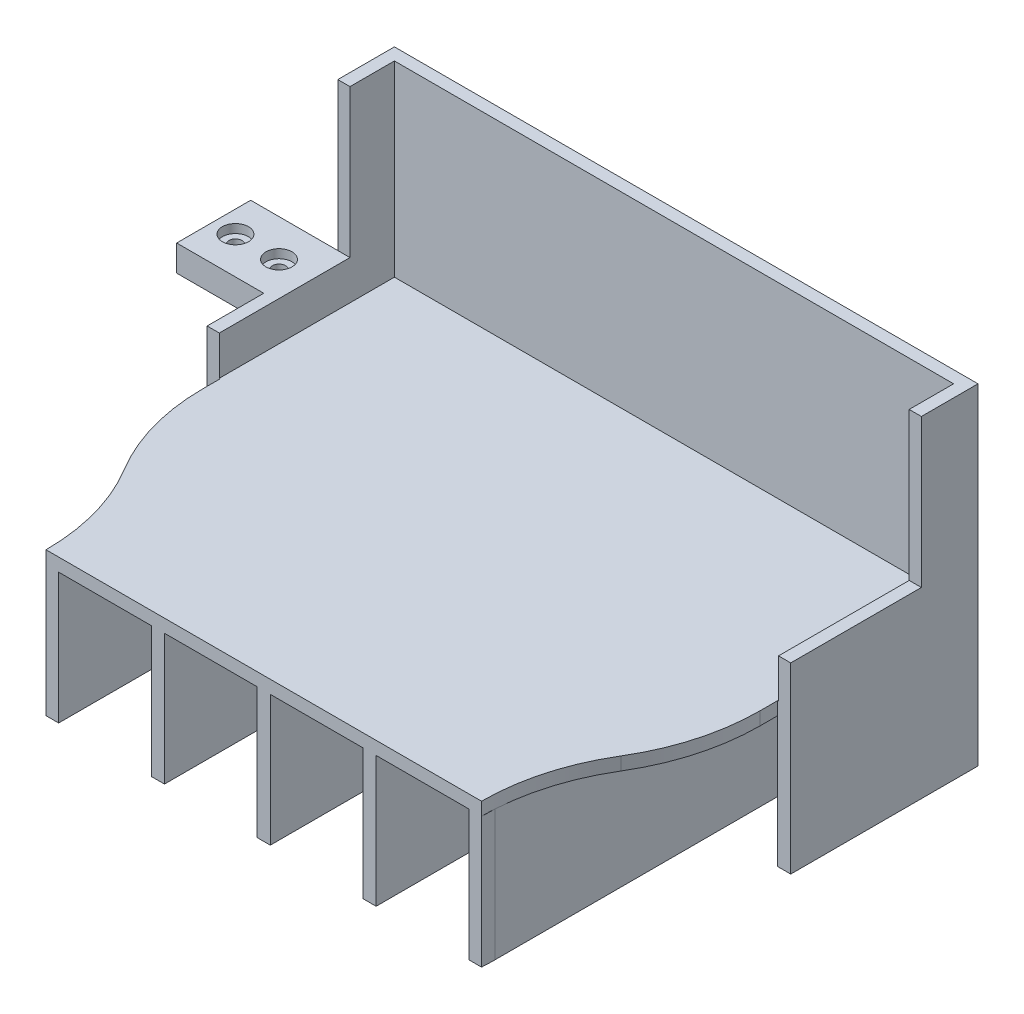
SolidWorks part; units mm, degrees
ref_plane "前视基准面" through (0, 0, 0) normal (0, 0, 1) x (1, 0, 0)
ref_plane "上视基准面" through (0, 0, 0) normal (0, 1, 0) x (1, 0, 0)
ref_plane "右视基准面" through (0, 0, 0) normal (1, 0, 0) x (0, 0, -1)
other "Configuration Table"
sketch "草图1" plane through (0, 0, 0) normal (0, 1, 0) x (1, 0, 0)
  line L6 (0, -20) -> (50, -20)
  line L23 (0, -20) -> (-50, -20)
  line L25 (-1, 70) -> (-1, 30)
  line L26 (1, 70) -> (41, 70)
  line L27 (43, 52) -> (85, 52)
  line L32 (1, 30) -> (41, 30)
  line L36 (1, 70) -> (1, 30)
  line L37 (-41, 30) -> (-1, 30)
  line L38 (-41, 70) -> (-1, 70)
  line L39 (-43, 72) -> (43, 72)
  line L40 (-43, 50) -> (-43, 10)
  line L41 (-41, 70) -> (-41, 30)
  line L42 (-43, 10) -> (-83, 10)
  line L43 (-83, 10) -> (-83, 50)
  line L44 (-83, 50) -> (-43, 50)
  line L45 (41, 70) -> (41, 30)
  line L46 (85, 8) -> (85, 52)
  line L48 (43, 10) -> (83, 10)
  line L49 (43, 52) -> (43, 72)
  line L50 (43, 50) -> (43, 10)
  line L51 (83, 10) -> (83, 50)
  line L52 (43, 50) -> (83, 50)
  line L61 (50, -20) -> (57, -20)
  line L63 (-50, -20) -> (-57, -20)
  line L64 (-85, 50) -> (-85, 8)
  line L65 (-85, 50) -> (-85, 52)
  line L66 (-85, 52) -> (-43, 52)
  line L67 (-43, 52) -> (-43, 72)
  circle A0 centre (18, 0) radius 10
  circle A1 centre (-18, 0) radius 10
  arc A3 (85, 8) -> (57, -20) centre (57, 8) cw
  arc A4 (-57, -20) -> (-85, 8) centre (-57, 8) cw
extrude "凸台-拉伸1" add sketch "草图1" along normal blind 2
sketch "草图2" plane through (0, 0, 0) normal (0, -1, 0) x (1, 0, 0)
  line L0 (-85, -8) -> (-85, -52)
  line L1 (-85, -52) -> (-43, -52)
  line L2 (-43, -52) -> (-43, -72)
  line L3 (-43, -72) -> (43, -72)
  line L4 (43, -72) -> (43, -52)
  line L5 (43, -52) -> (85, -52)
  line L6 (85, -52) -> (85, -8)
  line L7 (-57, 20) -> (57, 20)
  arc A0 (-85, -8) -> (-57, 20) centre (-57, -8) cw
  arc A1 (57, 20) -> (85, -8) centre (57, -8) cw
  circle A2 centre (-18, 0) radius 10
  circle A3 centre (18, 0) radius 10
extrude "凸台-拉伸2" add sketch "草图2" along normal blind 2
sketch "草图4" plane through (0, 2, 0) normal (0, 1, 0) x (1, 0, 0)
  line L0 (0, -20) -> (-50, -20)
  line L1 (-57, -20) -> (57, -20) construction
  line L2 (-50, -20) -> (50, -20)
  arc A0 (-50, -20) -> (50, -20) centre (0, -20) cw
  circle A3 centre (-18, 0) radius 15
  circle A4 centre (18, 0) radius 15
  line M14 (-57, -20) -> (57, -20)
extrude "凸台-拉伸3" add sketch "草图4" along normal blind 8 contours A0 A4 A3 M14 region at (0, 2, -1.9073)
loft "切除-放样1" cut section edge at (-18, 10, 15) section edge at (-18, 2, 10) end constraint default connector at (-3.9419, 10, -5.2315) connector at (-9.8366, 2, -5.7757)
sketch "草图5" plane through (0, 2, 0) normal (0, 1, 0) x (1, 0, 0)
  circle A0 centre (-18, 0) radius 10
sketch "草图6" plane through (0, 10, 0) normal (0, 1, 0) x (1, 0, 0)
  circle A0 centre (-18, 0) radius 15
sketch "草图7" plane through (0, 10, 0) normal (0, 1, 0) x (1, 0, 0)
  circle A0 centre (-18, 0) radius 15
  circle A1 centre (-18, 0) radius 10
extrude "凸台-拉伸4" add sketch "草图7" against normal blind 8 contours A0 | A1
loft "切除-放样2" cut profiles "草图6", "草图5" connector at (-3.6249, 10, -4.2843) connector at (-10.0221, 2, -6.0293)
sketch "草图9" plane through (0, 2, 0) normal (0, 1, 0) x (1, 0, 0)
  circle A0 centre (18, 0) radius 10
sketch "草图10" plane through (0, 10, 0) normal (0, 1, 0) x (1, 0, 0)
  circle A0 centre (18, 0) radius 15
sketch "草图11" plane through (0, 10, 0) normal (0, 1, 0) x (1, 0, 0)
  circle A0 centre (18, 0) radius 10
  circle A1 centre (18, 0) radius 15
extrude "凸台-拉伸5" add sketch "草图11" against normal blind 8
loft "切除-放样3" cut profiles "草图10", "草图9" connector at (32.657, 10, -3.1893) connector at (26.6644, 2, -4.9927)
fillet "圆角1" radius 8 1 edges at (0, 10, -30)
sketch "草图20" plane through (0, 2, 0) normal (0, 1, 0) x (1, 0, 0)
  circle A0 centre (-18, 0) radius 10
  circle A1 centre (18, 0) radius 10
extrude "凸台-拉伸7" add sketch "草图20" against normal blind 1
sketch "草图21" plane through (0, 2, 0) normal (0, 1, 0) x (1, 0, 0)
  line L0 (-42, -20) -> (42, -20) construction
  line L1 (-50, -20) -> (-42, -20) construction
  line L2 (-50, -20) -> (-103.4635, -20)
  line L3 (-103.4635, -20) -> (-103.4635, 85.0865)
  line L4 (50, -20) -> (103.2152, -20)
  line L5 (103.2152, -20) -> (103.2152, 85.0865)
  line L6 (103.2152, 85.0865) -> (-103.4635, 85.0865)
  arc A0 (-50, -20) -> (50, -20) centre (0, -20) cw
  arc A1 (50, -20) -> (-50, -20) centre (0, -20) ccw construction
extrude "切除-拉伸2" cut sketch "草图21" against normal blind 4
sketch "草图22" plane through (0, -2, 0) normal (0, -1, 0) x (1, 0, 0)
  line L22 (-64, -30) -> (-64, -74)
  line L23 (-64, -74) -> (0, -74)
  line L24 (64, -30) -> (64, -74)
  line L25 (64, -74) -> (0, -74)
  line L28 (50, 20) -> (-50, 20) construction
  arc A1 (-50, 20) -> (-57, -5) centre (-98.1429, 20) cw
  arc A2 (-64, -30) -> (-57, -5) centre (-15.8571, -30) cw
  arc A3 (64, -30) -> (57, -5) centre (15.8571, -30) ccw
  arc A4 (57, -5) -> (50, 20) centre (98.1429, 20) cw
  arc A5 (-50, 20) -> (50, 20) centre (0, 20) ccw
extrude "凸台-拉伸8" add sketch "草图22" against normal blind 4
sketch "草图28" plane through (0, -2, 0) normal (0, -1, 0) x (1, 0, 0)
  circle A0 centre (-18, 0) radius 10
  circle A1 centre (18, 0) radius 10
extrude "凸台-拉伸10" add sketch "草图28" against normal blind 4
sketch "草图29" plane through (0, 2, 0) normal (0, 1, 0) x (1, 0, 0)
  circle A0 centre (-18, 0) radius 10
  circle A1 centre (18, 0) radius 10
extrude "切除-拉伸5" cut sketch "草图29" against normal blind 3
sketch "草图31" plane through (0, 10, 0) normal (0, 1, 0) x (1, 0, 0)
  line L0 (-50, -20) -> (50, -20)
  arc A0 (-50, -20) -> (50, -20) centre (0, -20) cw
extrude "切除-拉伸6" cut sketch "草图31" against normal blind 8
sketch "草图32" plane through (0, 2, 0) normal (0, 1, 0) x (1, 0, 0)
  circle A0 centre (-18, 0) radius 10
  circle A1 centre (18, 0) radius 10
extrude "凸台-拉伸11" add sketch "草图32" against normal blind 4
sketch "草图33" plane through (0, 0, -74) normal (0, 0, -1) x (-1, 0, 0)
  line L0 (64, 2) -> (64, -2) construction
  line L1 (-64, 2) -> (64, 2)
  line L2 (-64, 2) -> (-64, 1)
  line L3 (-64, 1) -> (64, 1)
  line L4 (64, 2) -> (64, 1)
extrude "切除-拉伸7" cut sketch "草图33" against normal blind 100
sketch "草图34" plane through (0, 1, 0) normal (0, 1, 0) x (1, 0, 0)
  line L1 (-64, 74) -> (64, 74)
  line L2 (-64, 74) -> (-64, 77)
  line L3 (-64, 77) -> (64, 77)
  line L4 (64, 74) -> (64, 77)
  line L5 (64, 77) -> (67, 77)
  line L6 (64, 77) -> (64, 34)
  line L7 (64, 34) -> (67, 34)
  line L8 (67, 77) -> (67, 34)
  line L9 (-64, 77) -> (-67, 77)
  line L10 (-64, 77) -> (-64, 34)
  line L11 (-64, 34) -> (-67, 34)
  line L12 (-67, 77) -> (-67, 34)
  line M16 (64, 30) -> (64, 74)
  line M17 (64, 74) -> (-64, 74)
  line M18 (-64, 74) -> (-64, 30)
extrude "凸台-拉伸12" add sketch "草图34" along normal blind 42 separate body contours L8 L5 L4 L7 M16 | L4 L3 L2 M17 | L9 L12 L11 L2 M18 region at (0, 1, -75.5) region at (-65.5, 1, -55.5) region at (65.5, 1, -55.5)
sketch "草图35" plane through (0, -2, 0) normal (0, -1, 0) x (1, 0, 0)
  line L0 (-67, -77) -> (67, -77) construction
  line L1 (-67, -34) -> (-64, -34)
  line L2 (-67, -34) -> (-67, -77)
  line L3 (-67, -77) -> (-64, -77)
  line L4 (-64, -34) -> (-64, -77)
  line L6 (-64, -77) -> (64, -77)
  line L7 (-64, -77) -> (-64, -74)
  line L8 (-64, -74) -> (64, -74)
  line L9 (64, -77) -> (64, -74)
  line L10 (67, -34) -> (64, -34)
  line L11 (67, -34) -> (67, -77)
  line L12 (67, -77) -> (64, -77)
  line L13 (64, -34) -> (64, -77)
  line M9 (-64, -74) -> (64, -74)
  line M10 (64, -74) -> (64, -30)
extrude "凸台-拉伸13" add sketch "草图35" against normal blind 3 contours L6 L9 L4 M9 | L12 L11 L10 L9 M10 | L3 L2 L1 L4 region at (0, -2, -75.5) region at (65.5, -2, -55.5)
sketch "草图36" plane through (0, -2, 0) normal (0, -1, 0) x (1, 0, 0)
  line L0 (-67, -77) -> (67, -77) construction
  line L1 (-67, -34) -> (-64, -34)
  line L2 (-67, -34) -> (-67, -77)
  line L3 (-67, -77) -> (-64, -77)
  line L4 (-64, -34) -> (-64, -77)
  line L5 (64, -34) -> (64, -74)
  line L6 (64, -34) -> (67, -34)
  line L8 (64, -77) -> (67, -77)
  line L9 (67, -34) -> (67, -77)
  line L10 (-64, -77) -> (64, -77)
  line L11 (-64, -77) -> (-64, -74)
  line L12 (-64, -74) -> (64, -74)
  line L13 (64, -77) -> (64, -74)
  line L14 (64, -74) -> (64, -77)
  line M9 (67, -34) -> (64, -34)
  line M17 (-64, -34) -> (-67, -34)
  line M18 (-67, -34) -> (-67, -77)
  line M19 (-67, -77) -> (67, -77)
  line M20 (67, -77) -> (67, -34)
extrude "凸台-拉伸14" add sketch "草图36" along normal blind 30 contours L13 L5 M19 M20 M9 | L13 L12 L4 M19 | L4 M17 M18 M19 region at (-65.5, -2, -55.5) region at (0, -2, -75.5) region at (65.5, -2, -55.5)
sketch "草图37" plane through (0, -2, 0) normal (0, -1, 0) x (-1, 0, 0)
  line L2 (0, -17) -> (-50.0936, -17)
  line L3 (0, -17) -> (50.0936, -17)
  line L4 (50, -20) -> (-50, -20)
  arc A0 (-50, -20) -> (-57, 5) centre (-98.1429, -20) ccw construction
  arc A1 (57, 5) -> (50, -20) centre (98.1429, -20) ccw construction
  arc A2 (50.0936, -17) -> (50, -20) centre (1.9507, -17) cw
  arc A3 (-50.0936, -17) -> (-50, -20) centre (-1.9507, -17) ccw
extrude "凸台-拉伸15" add sketch "草图37" along normal blind 30
sketch "草图40" plane through (0, -2, 0) normal (0, -1, 0) x (1, 0, 0)
  line L0 (-64, -34) -> (64, -34)
  line L1 (64, -34) -> (64, -37)
  line L2 (64, -74) -> (64, -34) construction
  line L3 (64, -37) -> (-64, -37)
  line L4 (-64, -34) -> (-64, -74) construction
  line L5 (-64, -37) -> (-64, -34)
extrude "凸台-拉伸16" add sketch "草图40" along normal blind 30
sketch "草图41" plane through (0, -2, 0) normal (0, -1, 0) x (1, 0, 0)
  line L0 (64, -34) -> (-64, -34) construction
  line L1 (-50.0936, 17) -> (-47.0936, 17)
  line L2 (-50.0936, 17) -> (-50.0936, -34)
  line L3 (-50.0936, -34) -> (-47.0936, -34)
  line L4 (-47.0936, 17) -> (-47.0936, -34)
  line L6 (50.0936, 17) -> (47.0936, 17)
  line L7 (50.0936, 17) -> (50.0936, -34)
  line L8 (50.0936, -34) -> (47.0936, -34)
  line L9 (47.0936, 17) -> (47.0936, -34)
extrude "凸台-拉伸17" add sketch "草图41" along normal blind 30
sketch "草图42" plane through (0, 43, 0) normal (0, 1, 0) x (1, 0, 0)
  line L0 (-64, 74.2) -> (64, 74.2)
  line L1 (-64, 74) -> (-64.2, 74)
  line L2 (-64, 74) -> (-64, 74.2)
  line L3 (-64, 74.2) -> (-64.2, 74.2)
  line L4 (-64.2, 74) -> (-64.2, 74.2)
  line L5 (64, 74) -> (64.2, 74)
  line L6 (64, 74) -> (64, 74.2)
  line L7 (64, 74.2) -> (64.2, 74.2)
  line L8 (64.2, 74) -> (64.2, 74.2)
  line L9 (64.2, 74) -> (64.2, 34)
  line L10 (64, 34) -> (67, 34) construction
  line L11 (64.2, 34) -> (64, 34)
  line L12 (64, 34) -> (64, 74)
  line L13 (64, 74) -> (-64, 74)
  line L14 (-64.2, 74) -> (-64.2, 34)
  line L15 (-64, 34) -> (-67, 34) construction
  line L16 (-64.2, 34) -> (-64, 34)
  line L17 (-64, 34) -> (-64, 74)
  line M12 (-67, 34) -> (-64, 34)
  line M13 (-64, 34) -> (-64, 74)
  line M14 (-64, 74) -> (64, 74)
  line M15 (64, 74) -> (64, 34)
  line M16 (64, 34) -> (67, 34)
extrude "切除-拉伸8" cut sketch "草图42" against normal blind 42 contours L6 L0 L2 M14 | L4 L1 L2 L3 | L1 L14 M12 M13 | L9 L5 M15 M16 | L5 L8 L7 L6 region at (0, 43, -74.1) region at (-64.1, 43, -74.1) region at (64.1, 43, -74.1) region at (-64.1, 43, -54) region at (64.1, 43, -54)
sketch "草图43" plane through (-67, 0, 0) normal (-1, 0, 0) x (0, 0, 1)
  line L0 (-77, -32) -> (-77, -2)
  line L1 (-77, 43) -> (-77, -32) construction
  line L6 (-55.5, 4) -> (-45.5, 4)
  line L7 (-55.5, 4) -> (-65.5, 4)
  line L8 (-65.5, 4) -> (-65.5, -2)
  line L9 (-45.5, 4) -> (-45.5, -2)
  line L10 (-45.5, -2) -> (-65.5, -2)
extrude "凸台-拉伸18" add sketch "草图43" along normal blind 20 contours L10 L9 L6 L7 L8 region at (-67, 1, -55.5)
sketch "草图44" plane through (0, 4, 0) normal (0, 1, 0) x (1, 0, 0)
  line L0 (-87, 65.5) -> (-67, 45.5)
  circle A0 centre (-77, 55.5) radius 2.6
extrude "切除-拉伸9" cut sketch "草图44" against normal blind 20 contours L0 A0 | L0 A0 region at (-76.2197, 4, -56.2803) region at (-77.7803, 4, -54.7197)
sketch "草图45" plane through (0, 4, 0) normal (0, 1, 0) x (1, 0, 0)
  circle A0 centre (-77, 55.5) radius 5
extrude "切除-拉伸10" cut sketch "草图45" against normal blind 3
sketch "草图46" plane through (-67, 0, 0) normal (-1, 0, 0) x (0, 0, 1)
  line L0 (-34, 43) -> (-42, 43)
  line L5 (-77, 43) -> (-69, 43)
  line L6 (-64, 43) -> (-47, 43)
  line L7 (-64, 43) -> (-64, 10)
  line L8 (-47, 43) -> (-47, 10)
  line L9 (-47, 10) -> (-64, 10)
  line L10 (-64, 10) -> (-64, 4)
  line L11 (-64, 4) -> (-47, 4)
  line L12 (-47, 4) -> (-47, 10)
  circle A1 centre (-69, 43) radius 5
  circle A2 centre (-42, 43) radius 5
  line M13 (-65.5, 4) -> (-45.5, 4)
extrude "凸台-拉伸19" add sketch "草图46" along normal blind 20 contours L12 L9 L10 M13 region at (-67, 7, -55.5)
sketch "草图47" plane through (-87, 0, 0) normal (-1, 0, 0) x (0, 0, 1)
  line L1 (-65.5, -2) -> (-45.5, -2)
  line L2 (-65.5, -2) -> (-65.5, 4)
  line L3 (-65.5, 4) -> (-45.5, 4)
  line L4 (-45.5, -2) -> (-45.5, 4)
extrude "切除-拉伸11" cut sketch "草图47" against normal blind 20
sketch "草图48" plane through (0, 10, 0) normal (0, 1, 0) x (1, 0, 0)
  line L0 (-87, 64) -> (-87, 47)
  line L2 (-67, 77) -> (-67, 34) construction
  line L3 (-77, 55.5) -> (-67, 55.5)
  line L4 (-77, 55.5) -> (-87, 55.5)
  circle A0 centre (-82, 55.5) radius 1.5
  circle A1 centre (-72, 55.5) radius 1.5
extrude "切除-拉伸12" cut sketch "草图48" against normal blind 20 contours L4 A0 | L4 A0 | L3 A1 | L3 A1 region at (-72, 10, -56.1366) region at (-72, 10, -54.8634) region at (-82, 10, -54.8634) region at (-82, 10, -56.1366)
sketch "草图49" plane through (0, 10, 0) normal (0, 1, 0) x (1, 0, 0)
  circle A0 centre (-82, 55.5) radius 3
  circle A1 centre (-72, 55.5) radius 3
extrude "切除-拉伸13" cut sketch "草图49" against normal blind 2
sketch "草图50" plane through (-67, 0, 0) normal (-1, 0, 0) x (0, 0, 1)
  line L1 (-64, 10) -> (-34, 10)
  line L2 (-64, 10) -> (-64, 43)
  line L3 (-64, 43) -> (-34, 43)
  line L4 (-34, 10) -> (-34, 43)
extrude "切除-拉伸14" cut sketch "草图50" against normal blind 3
sketch "草图51" plane through (0, 43, 0) normal (0, 1, 0) x (1, 0, 0)
  line L1 (-64.2, 64) -> (-67, 64)
  line L2 (-64.2, 64) -> (-64.2, 77)
  line L3 (-64.2, 77) -> (-67, 77)
  line L4 (-67, 64) -> (-67, 77)
  line L5 (-64.2, 77) -> (64.2, 77)
  line L6 (-64.2, 77) -> (-64.2, 74.2)
  line L7 (-64.2, 74.2) -> (64.2, 74.2)
  line L8 (64.2, 77) -> (64.2, 74.2)
  line L9 (64.2, 34) -> (67, 34)
  line L10 (64.2, 34) -> (64.2, 77)
  line L11 (64.2, 77) -> (67, 77)
  line L12 (67, 34) -> (67, 77)
  line M5 (-67, 64) -> (-64.2, 64)
  line M6 (-64.2, 64) -> (-64.2, 74.2)
  line M7 (-64.2, 74.2) -> (64.2, 74.2)
  line M8 (64.2, 74.2) -> (64.2, 34)
  line M9 (64.2, 34) -> (67, 34)
  line M10 (67, 34) -> (67, 77)
  line M11 (67, 77) -> (-67, 77)
  line M12 (-67, 77) -> (-67, 64)
extrude "凸台-拉伸20" add sketch "草图51" along normal blind 1 contours L8 L2 M11 M7 | L2 M6 M11 M12 M5 | L8 M11 M8 M9 M10 region at (-65.6, 43, -70.5) region at (0, 43, -75.6) region at (65.6, 43, -55.5)
sketch "草图52" plane through (0, -32, 0) normal (0, -1, 0) x (1, 0, 0)
  line L0 (50, 20) -> (-50, 20) construction
  line L1 (-64, -37) -> (64, -37)
  line L2 (-64, -37) -> (-64, -34)
  line L3 (-64, -34) -> (64, -34)
  line L4 (64, -37) -> (64, -34)
  line L5 (-47.0936, 17) -> (47.0936, 17)
  line L6 (-47.0936, 17) -> (-47.0936, 20)
  line L7 (-47.0936, 20) -> (47.0936, 20)
  line L8 (47.0936, 17) -> (47.0936, 20)
extrude "切除-拉伸15" cut sketch "草图52" against normal blind 30
sketch "草图53" plane through (0, -2, 0) normal (0, -1, 0) x (1, 0, 0)
  line L0 (-64, -74) -> (64, -74) construction
  line L1 (-50.0936, -34) -> (-47.0936, -34)
  line L2 (-50.0936, -34) -> (-50.0936, -74)
  line L3 (-50.0936, -74) -> (-47.0936, -74)
  line L4 (-47.0936, -34) -> (-47.0936, -74)
  line L5 (-64, -74) -> (64, -74) construction
  line L6 (47.0936, -34) -> (50.0936, -34)
  line L7 (47.0936, -34) -> (47.0936, -74)
  line L8 (47.0936, -74) -> (50.0936, -74)
  line L9 (50.0936, -34) -> (50.0936, -74)
extrude "凸台-拉伸21" add sketch "草图53" along normal blind 30
sketch "草图54" plane through (0, -2, 0) normal (0, -1, 0) x (1, 0, 0)
  line L0 (-47.0936, 20) -> (-1.5, 20)
  line L1 (-22.7968, -74) -> (-22.7968, 20)
  line L2 (1.5, 20) -> (47.0936, 20)
  line L3 (-47.0936, -74) -> (47.0936, -74) construction
  line L4 (-24.2968, 20) -> (-24.2968, -74)
  line L5 (47.0936, 20) -> (-47.0936, 20) construction
  line L6 (-1.5, -74) -> (1.5, -74)
  line L7 (-1.5, -74) -> (-1.5, 20)
  line L8 (-1.5, 20) -> (1.5, 20)
  line L9 (1.5, -74) -> (1.5, 20)
  line L10 (-47.0936, -74) -> (47.0936, -74) construction
  line L11 (24.2968, 20) -> (24.2968, -74)
  line L12 (-24.2968, -74) -> (-22.7968, -74)
  line L13 (-24.2968, -27) -> (-25.7968, -27)
  line L14 (-25.7968, -27) -> (-25.7968, 20)
  line L15 (-25.7968, 20) -> (-22.7968, 20)
  line L16 (-25.7968, -27) -> (-25.7968, -74)
  line L17 (-25.7968, -74) -> (-22.7968, -74)
  line L18 (24.2968, -27) -> (25.7996, -27)
  line L19 (24.2968, -27) -> (22.7968, -27)
  line L20 (22.7968, -27) -> (22.7968, -74)
  line L21 (25.7996, -27) -> (25.7996, -74)
  line L22 (25.7996, -74) -> (22.7968, -74)
  line L23 (22.7968, -27) -> (22.7968, 20)
  line L24 (22.7968, 20) -> (25.7996, 20)
  line L25 (25.7996, 20) -> (25.7996, -27)
  line M9 (-47.0936, -74) -> (47.0936, -74)
  line M11 (47.0936, 20) -> (-47.0936, 20)
extrude "凸台-拉伸23" add sketch "草图54" along normal blind 30 contours L0 L4 L1 M9 | L14 L13 L4 M11 | L13 L16 L4 M9 | L9 L7 M9 M11 | L25 L2 L11 L18 | L23 L19 L11 L2 | L19 L20 L11 M9 | L21 L18 L11 M9 region at (-25.0468, -2, -3.5) region at (-23.5468, -2, -27) region at (-25.0468, -2, -50.5) region at (0, -2, -27) region at (23.5468, -2, -3.5) region at (23.5468, -2, -50.5) region at (25.0482, -2, -3.5) region at (25.0482, -2, -50.5)
sketch "草图55" plane through (-67, 0, 0) normal (-1, 0, 0) x (0, 0, 1)
  line L1 (-64, 10) -> (-34, 10)
  line L2 (-64, 10) -> (-64, 44)
  line L3 (-64, 44) -> (-34, 44)
  line L4 (-34, 10) -> (-34, 44)
extrude "切除-拉伸16" cut sketch "草图55" against normal blind 200
